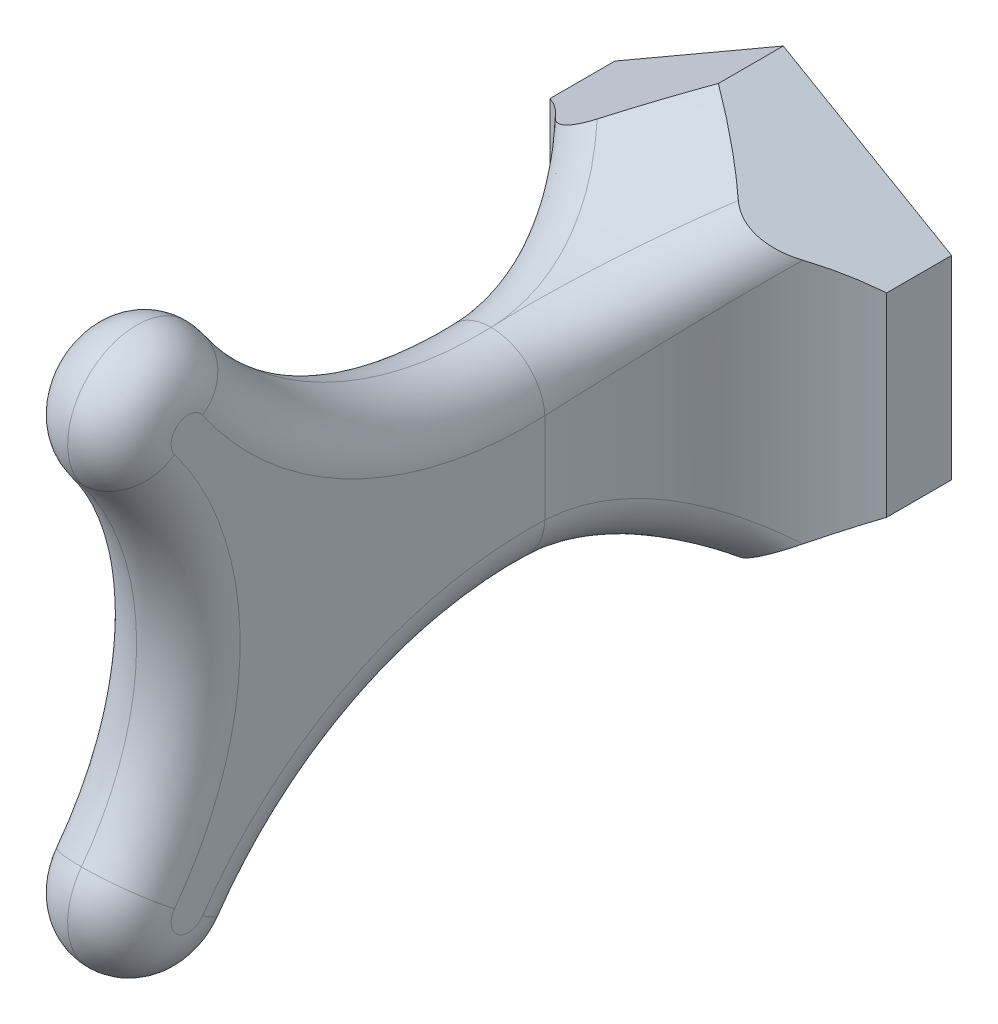
SolidWorks part; units mm, degrees
ref_plane "Front Plane" through (0, 0, 0) normal (0, 0, 1) x (1, 0, 0)
ref_plane "Top Plane" through (0, 0, 0) normal (0, 1, 0) x (1, 0, 0)
ref_plane "Right Plane" through (0, 0, 0) normal (1, 0, 0) x (0, 0, -1)
sketch "Sketch1" plane through (0, 0, 0) normal (0, 0, 1) x (1, 0, 0)
  line L6 (-15.875, 794.4957) -> (-15.875, 776.1649)
  line L7 (-15.875, 776.1649) -> (0, 766.9994)
  line L8 (0, 766.9994) -> (15.875, 776.1649)
  line L9 (15.875, 776.1649) -> (15.875, 794.4957)
  line L10 (15.875, 794.4957) -> (0, 803.6612)
  line L11 (0, 803.6612) -> (-15.875, 794.4957)
  line L12 (-15.875, 794.4957) -> (-15.875, 776.1649)
  line L13 (-15.875, 776.1649) -> (0, 766.9994)
  line L14 (0, 766.9994) -> (15.875, 776.1649)
  line L15 (15.875, 776.1649) -> (15.875, 794.4957)
  line L16 (15.875, 794.4957) -> (0, 803.6612)
  line L17 (0, 803.6612) -> (-15.875, 794.4957)
  line L24 (-15.494, 794.2758) -> (-15.494, 776.3848)
  line L25 (-15.494, 776.3848) -> (0, 767.4394)
  line L26 (0, 767.4394) -> (15.494, 776.3848)
  line L27 (15.494, 776.3848) -> (15.494, 794.2758)
  line L28 (15.494, 794.2758) -> (0, 803.2212)
  line L29 (0, 803.2212) -> (-15.494, 794.2758)
  line L30 (-15.494, 794.2758) -> (-15.494, 776.3848)
  line L31 (-15.494, 776.3848) -> (0, 767.4394)
  line L32 (0, 767.4394) -> (15.494, 776.3848)
  line L33 (15.494, 776.3848) -> (15.494, 794.2758)
  line L34 (15.494, 794.2758) -> (0, 803.2212)
  line L35 (0, 803.2212) -> (-15.494, 794.2758)
  dimension "D1" = 0
  dimension "D2" = 0.381
extrude "Boss-Extrude1" add sketch "Sketch1" along normal offset from surface (5.969 mm away) 0.381 contours L34 L35 L30 L31 L32 L33 region at (0, 785.3303, 0)
ref_plane "Plane1" through (0, 0, 56.769) normal (0, 0, 1) x (1, 0, 0)
sketch "Sketch2" plane through (0, 0, 0) normal (1, 0, 0) x (0, 0, -1)
  line L0 (-5.969, 785.3303) -> (-51.2485, 785.3303) construction
  line L1 (-5.969, 794.2758) -> (-5.969, 776.3848) construction
  line L2 (-5.969, 803.2212) -> (-5.969, 767.4394)
  arc A0 (-54.2775, 807.9786) -> (-5.969, 803.2212) centre (-28.1172, 825.9703) ccw
  arc A1 (-64.5896, 770.0903) -> (-64.5896, 800.5703) centre (-84.9096, 785.3303) ccw
  arc A2 (-54.2775, 807.9786) -> (-64.5896, 800.5703) centre (-59.5096, 804.3803) ccw
  arc A3 (-54.2775, 762.682) -> (-64.5896, 770.0903) centre (-59.5096, 766.2803) cw
  arc A4 (-54.2775, 762.682) -> (-5.969, 767.4394) centre (-28.1172, 744.6903) cw
  point P5 (-28.1172, 794.2203)
  point P18 (-64.9401, 801.1119)
  dimension "D1" = 63.5
  dimension "D2" = 50.8
  dimension "D3" = 12.7
  dimension "D4" = 8.89
  dimension "D5" = 19.05
extrude "Boss-Extrude2" add sketch "Sketch2" along normal mid plane 9.525
fillet "Fillet1" radius 25.4 2 edges at (4.7625, 785.3303, 5.969) (-4.7625, 785.3303, 5.969)
sketch "Sketch3" plane through (0, 0, 5.969) normal (0, 0, -1) x (-1, 0, 0)
  line L0 (0, 803.2212) -> (-15.494, 803.2212) construction
  line L1 (-15.494, 803.2212) -> (-15.494, 794.2758) construction
  line L2 (-15.494, 794.2758) -> (0, 803.2212) construction
  line L3 (15.494, 803.2212) -> (0, 803.2212) construction
  line L4 (0, 803.2212) -> (15.494, 794.2758) construction
  line L5 (15.494, 794.2758) -> (15.494, 803.2212) construction
  line L6 (0, 767.4394) -> (15.494, 767.4394) construction
  line L7 (15.494, 767.4394) -> (15.494, 776.3848) construction
  line L8 (15.494, 776.3848) -> (0, 767.4394) construction
  line L9 (-15.494, 767.4394) -> (0, 767.4394) construction
  line L10 (0, 767.4394) -> (-15.494, 776.3848) construction
  line L11 (-15.494, 776.3848) -> (-15.494, 767.4394) construction
  line L12 (0, 803.2212) -> (-15.494, 803.2212)
  line L13 (-15.494, 803.2212) -> (-15.494, 794.2758)
  line L14 (-15.494, 794.2758) -> (0, 803.2212)
  line L15 (15.494, 803.2212) -> (0, 803.2212)
  line L16 (0, 803.2212) -> (15.494, 794.2758)
  line L17 (15.494, 794.2758) -> (15.494, 803.2212)
  line L18 (0, 767.4394) -> (15.494, 767.4394)
  line L19 (15.494, 767.4394) -> (15.494, 776.3848)
  line L20 (15.494, 776.3848) -> (0, 767.4394)
  line L21 (-15.494, 767.4394) -> (0, 767.4394)
  line L22 (0, 767.4394) -> (-15.494, 776.3848)
  line L23 (-15.494, 776.3848) -> (-15.494, 767.4394)
  line M1 (-15.494, 767.4394) -> (0, 767.4394)
  line M2 (0, 767.4394) -> (-15.494, 776.3848)
  line M3 (-15.494, 776.3848) -> (-15.494, 767.4394)
extrude "Cut-Extrude1" cut sketch "Sketch3" against normal blind 12.7 contours M3 M1 M2 | L19 L20 L18 | L16 L17 L15 | L13 L14 L12 region at (10.3293, 800.2394, 5.969) region at (-10.3293, 800.2394, 5.969) region at (-10.3293, 770.4212, 5.969) region at (10.3293, 770.4212, 5.969)
fillet "Fillet2" radius 4.7625 14 edges at (5.8825, 775.1758, 19.2461) (4.7625, 773.1127, 42.2674) (4.7625, 761.1232, 63.2145) (4.7625, 785.3303, 59.5096) (4.7625, 809.5374, 63.2145) (4.7625, 797.5479, 42.2674) (-5.8825, 795.4848, 19.2461) (-5.8126, 775.2422, 19.4774) (-4.7625, 773.1127, 42.2674) (-4.7625, 761.1232, 63.2145) (-4.7625, 785.3303, 59.5096) (-4.7625, 809.5374, 63.2145) (5.8126, 795.4184, 19.4774) (-4.7625, 797.5479, 42.2674)
